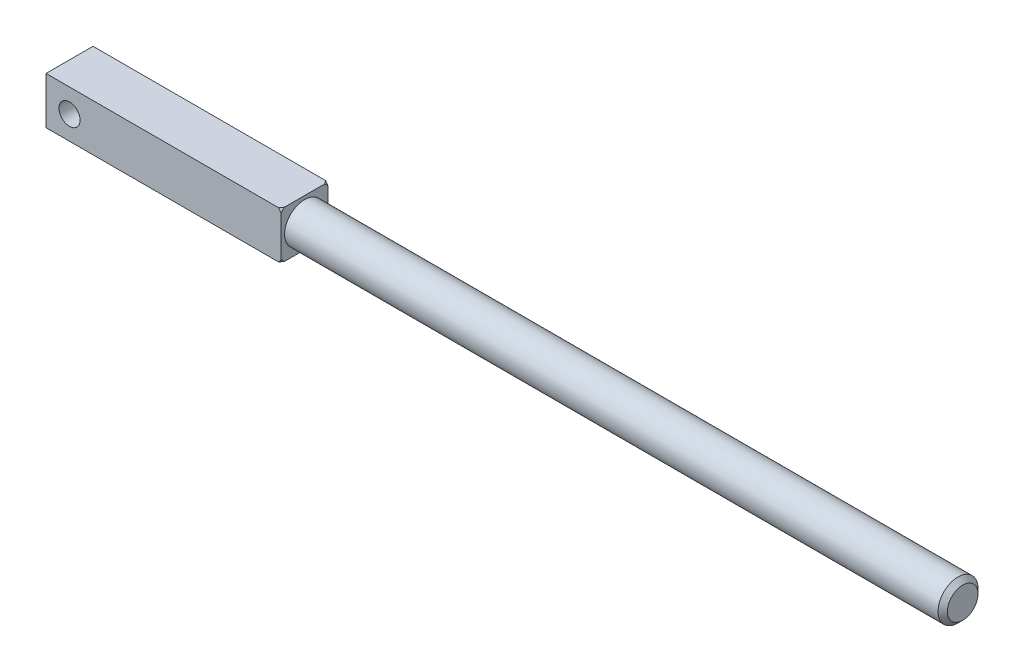
SolidWorks part; units mm, degrees
ref_plane "Front Plane" through (0, 0, 0) normal (0, 0, 1) x (1, 0, 0)
ref_plane "Top Plane" through (0, 0, 0) normal (0, 1, 0) x (1, 0, 0)
ref_plane "Right Plane" through (0, 0, 0) normal (1, 0, 0) x (0, 0, -1)
sketch "Sketch1" plane through (0, 0, 0) normal (1, 0, 0) x (0, 0, -1)
  line L1 (-5, 5) -> (5, 5)
  line L2 (-5, 5) -> (-5, -5)
  line L3 (-5, -5) -> (5, -5)
  line L4 (5, 5) -> (5, -5)
  dimension "D1" = 10
  dimension "D2" = 10
  dimension "D3" = 5
  dimension "D4" = 5
extrude "Boss-Extrude1" add sketch "Sketch1" along normal blind 50
sketch "Sketch3" plane through (50, 0, 0) normal (1, 0, 0) x (0, 0, -1)
  circle A0 centre (0, 0) radius 4.25
  dimension "D1" = 8.5
extrude "Boss-Extrude2" add sketch "Sketch3" along normal blind 140
chamfer "Chamfer1" distance 1 angle 45 1 edges at (190, 0, -4.25)
ref_plane "Plane1" through (0, 0, 0) normal (0, -0.7071, -0.7071) x (-1, 0, 0)
sketch "Sketch5" plane through (0, 0, 0) normal (0, -0.7071, -0.7071) x (-1, 0, 0)
  line L0 (-50, 7.0711) -> (-50, 6.5711)
  line L1 (-50, 0) -> (-50, 7.0711) construction
  line L2 (-50, 6.5711) -> (-49.5, 7.0711)
  line L3 (-50, 7.0711) -> (0, 7.0711) construction
  line L4 (-49.5, 7.0711) -> (-50, 7.0711)
  dimension "D1" = 0.5
  dimension "D2" = 0.5
sketch "Sketch6" plane through (0, 0, 0) normal (0, 1, 0) x (1, 0, 0)
  line L0 (-14.5231, 0) -> (199.2613, 0)
revolve "Cut-Revolve1" cut sketch "Sketch5" angle 360 about L0
sketch "Sketch7" plane through (0, 0, -5) normal (0, 0, -1) x (-1, 0, 0)
  line L3 (0, -5) -> (0, 5) construction
  line L4 (-49.5, 5) -> (0, 5) construction
  circle A2 centre (-5, 0) radius 2.25
  circle A3 centre (-5, 0) radius 4
  point P8 (-5, 0)
  dimension "D1" = 5
  dimension "D3" = 8
  dimension "D4" = 4.5
  dimension "D2" = 5
extrude "Cut-Extrude3" cut sketch "Sketch7" against normal blind 4.5 contours A3
extrude "Cut-Extrude4" cut sketch "Sketch7<5>" against normal blind 20 contours A2
sketch "Sketch7<5>" plane through (0, 0, -5) normal (0, 0, -1) x (-1, 0, 0) same geometry as "Sketch7"
